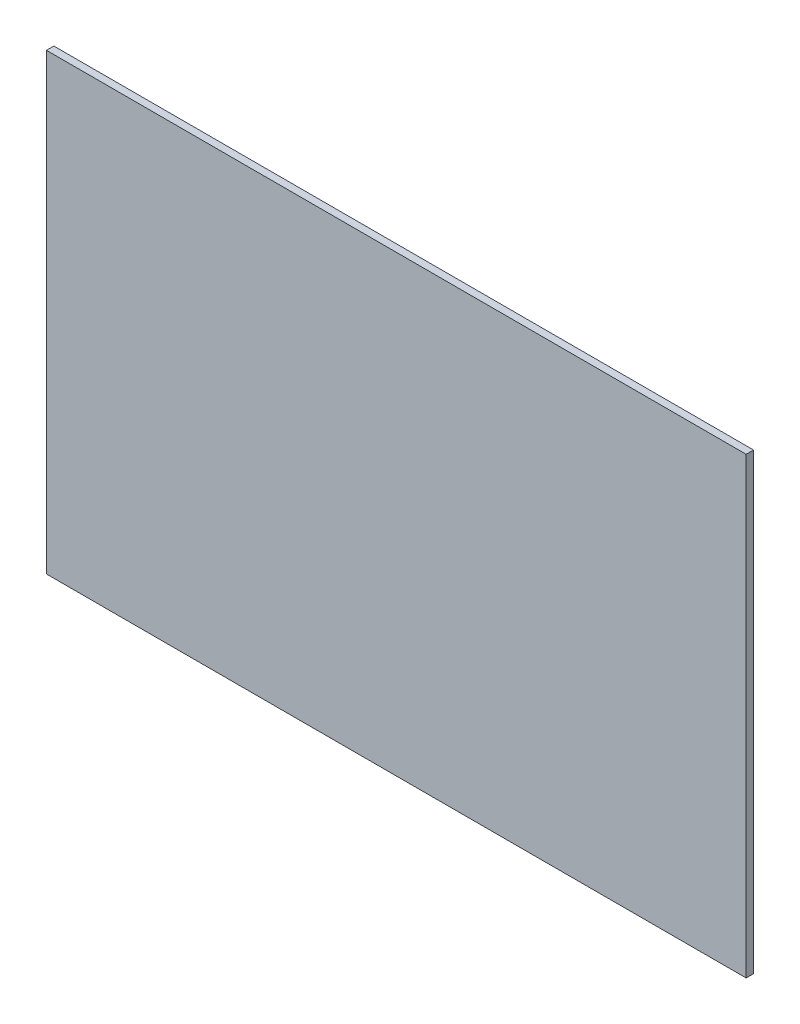
SolidWorks part; units mm, degrees
material "ABS"
ref_plane "X-Y Datum" through (0, 0, 0) normal (0, 0, 1) x (1, 0, 0)
ref_plane "X-Z Datum" through (0, 0, 0) normal (0, 1, 0) x (1, 0, 0)
ref_plane "Y-Z Datum" through (0, 0, 0) normal (1, 0, 0) x (0, 0, -1)
sketch "Sketch1" plane through (0, 0, 0) normal (0, 0, 1) x (1, 0, 0)
  line L0 (-149.85, 97.125) -> (-149.85, -97.125)
  line L1 (-149.85, 97.125) -> (149.85, 97.125)
  line L2 (-149.85, 97.125) -> (-149.85, -97.125)
  line L3 (-149.85, -97.125) -> (149.85, -97.125)
  line L4 (149.85, 97.125) -> (149.85, -97.125)
  line L5 (-149.85, 97.125) -> (149.85, -97.125) construction
  line L6 (-149.85, -97.125) -> (149.85, 97.125) construction
  line L7 (-149.85, -97.125) -> (149.85, -97.125)
  line L8 (149.85, 97.125) -> (149.85, -97.125)
  line L9 (-149.85, 97.125) -> (149.85, 97.125)
  circle A0 centre (-139.075, -86.35) radius 10.775
  circle A1 centre (-115.075, -86.35) radius 10.775 construction
  circle A2 centre (-127.075, -63.35) radius 10.775
  point P0 (0, 0)
  dimension "D1" = 21.55
  dimension "D2" = 24
  dimension "D3" = 23
  dimension "D4" = 12
  dimension "D5" = 194.25
  dimension "D6" = 299.7
  dimension "D7" = 0
extrude "Boss-Extrude1" add sketch "Sketch1" along normal blind 3.175 contours A0 L3 L4 L1 L2 A2 | A2 | A0 | A0 L2 L3 | L9 L0 L7 L8 L1 L4 L3 L2 region at (1.7533, 0.9913, 0) region at (-147.4432, -94.7182, 0) region at (-139.075, -86.35, 0) region at (-127.075, -63.35, 0)
